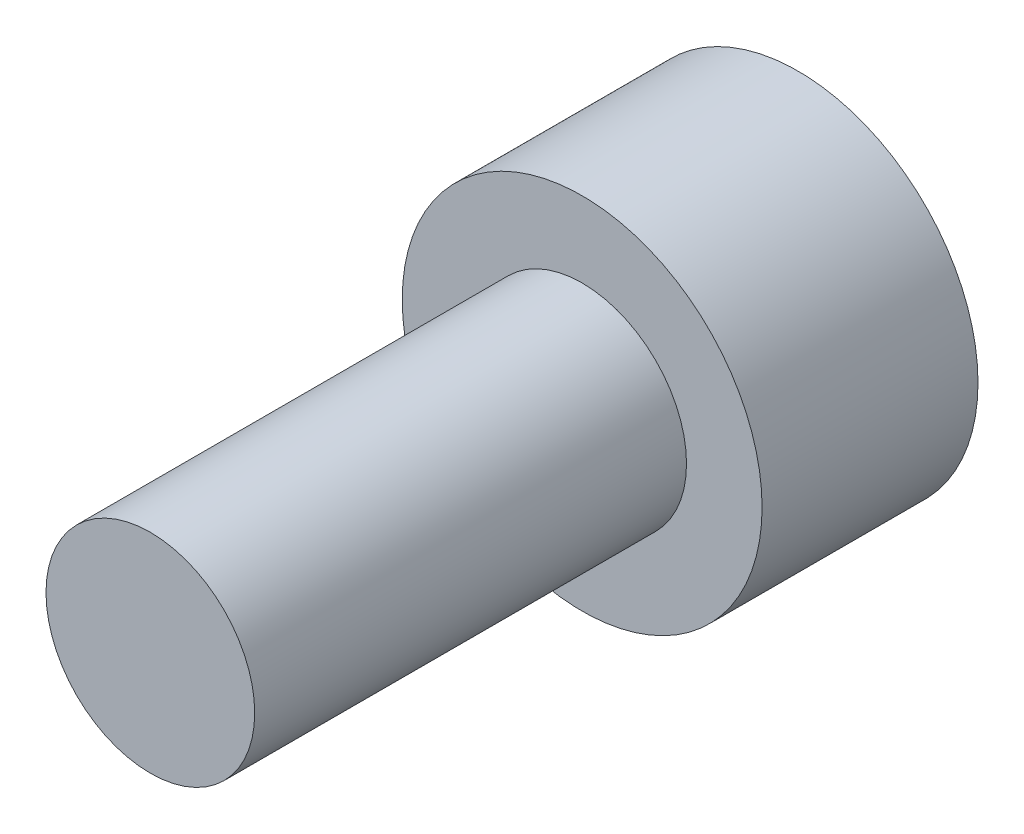
SolidWorks part; units mm, degrees
ref_plane "Front" through (0, 0, 0) normal (0, 0, 1) x (1, 0, 0)
ref_plane "Top" through (0, 0, 0) normal (0, 1, 0) x (1, 0, 0)
ref_plane "Right" through (0, 0, 0) normal (1, 0, 0) x (0, 0, -1)
sketch "Skizze1" plane through (0, 0, 0) normal (0, 0, 1) x (1, 0, 0)
  circle A0 centre (0, 0) radius 5
  circle A1 centre (0, 0) radius 2.9
  dimension "D1" = 5.8
  dimension "D2" = 10
extrude "Aufsatz-Linear austragen1" add sketch "Skizze1" along normal blind 18 contours A1 region at (0, 0, 0)
extrude "Aufsatz-Linear austragen2" add sketch "Skizze1<3>" along normal blind 6 contours A0 A1 region at (-4.8586, 0, 0)
sketch "Skizze1<3>" plane through (0, 0, 0) normal (0, 0, 1) x (1, 0, 0) same geometry as "Skizze1"
